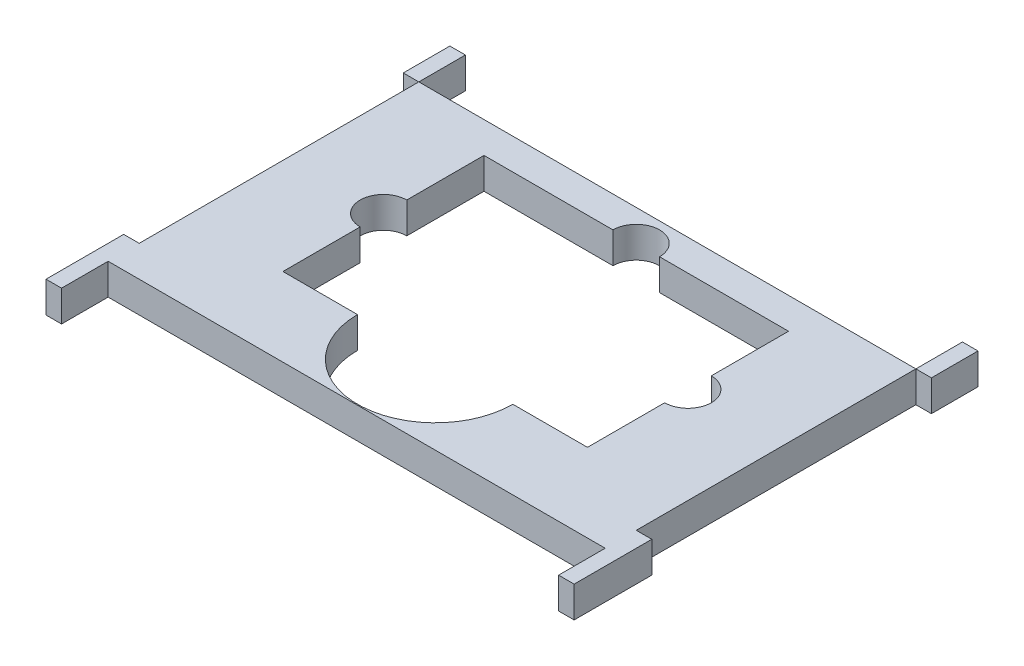
SolidWorks part; units mm, degrees
ref_plane "Front Plane" through (0, 0, 0) normal (0, 0, 1) x (1, 0, 0)
ref_plane "Top Plane" through (0, 0, 0) normal (0, 1, 0) x (1, 0, 0)
ref_plane "Right Plane" through (0, 0, 0) normal (1, 0, 0) x (0, 0, -1)
sketch "Sketch7" plane through (0, 0, 0) normal (0, 1, 0) x (1, 0, 0)
  line L1 (101.6, 63.5) -> (-101.6, 63.5)
  line L2 (101.6, 63.5) -> (101.6, -63.5)
  line L3 (101.6, -63.5) -> (-101.6, -63.5)
  line L4 (-101.6, 63.5) -> (-101.6, -63.5)
  line L5 (0, -63.5) -> (0, 63.5) construction
  line L6 (101.6, 0) -> (-101.6, 0) construction
  line L7 (-62.25, 50.8) -> (62.25, 50.8)
  line L8 (-62.25, 50.8) -> (-62.25, -31.4)
  line L9 (-62.25, -31.4) -> (62.25, -31.4)
  line L10 (62.25, 50.8) -> (62.25, -31.4)
  line L78 (-63.754, 177.8) -> (-101.6, 177.8) construction
  line L79 (63.754, 177.8) -> (101.6, 177.8) construction
  point P0 (0, 0)
  point P4 (0, 50.8)
  dimension "D1" = 124.5
  dimension "D2" = 82.2
  dimension "D3" = 127
  dimension "D9" = 203.2
  dimension "D4" = 12.7
extrude "Boss-Extrude4" add sketch "Sketch7" along normal blind 12.7
sketch "Sketch8" plane through (0, 0, 0) normal (0, 1, 0) x (1, 0, 0)
  line L0 (-101.6, 63.5) -> (-101.6, 69.85)
  line L1 (-101.6, 69.85) -> (-88.9, 69.85)
  line L2 (-88.9, 69.85) -> (-88.9, 63.5)
  line L3 (101.6, 63.5) -> (-101.6, 63.5) construction
  line L4 (-101.6, 63.5) -> (-88.9, 63.5)
  line L5 (-63.5, 63.5) -> (-63.5, 69.85)
  line L6 (-63.5, 69.85) -> (-50.8, 69.85)
  line L7 (-50.8, 69.85) -> (-50.8, 63.5)
  line L8 (-63.5, 63.5) -> (-50.8, 63.5)
  line L9 (-25.4, 63.5) -> (-25.4, 69.85)
  line L10 (-25.4, 69.85) -> (-12.7, 69.85)
  line L11 (-12.7, 69.85) -> (-12.7, 63.5)
  line L12 (-25.4, 63.5) -> (-12.7, 63.5)
  line L13 (12.7, 63.5) -> (12.7, 69.85)
  line L14 (12.7, 69.85) -> (25.4, 69.85)
  line L15 (25.4, 69.85) -> (25.4, 63.5)
  line L16 (12.7, 63.5) -> (25.4, 63.5)
  line L29 (50.8, 63.5) -> (50.8, 69.85)
  line L58 (-101.6, 63.5) -> (-107.95, 63.5)
  line L59 (-101.6, 63.5) -> (-101.6, -63.5) construction
  line L60 (-107.95, 63.5) -> (-107.95, 50.8)
  line L61 (-107.95, 50.8) -> (-101.6, 50.8)
  line L62 (-101.6, 63.5) -> (-101.6, 50.8)
  line L63 (-107.95, 12.7) -> (-101.6, 12.7)
  line L64 (-101.6, 25.4) -> (-101.6, 12.7)
  line L65 (-101.6, 25.4) -> (-107.95, 25.4)
  line L66 (-107.95, 25.4) -> (-107.95, 12.7)
  line L67 (-107.95, -25.4) -> (-101.6, -25.4)
  line L68 (-101.6, -12.7) -> (-101.6, -25.4)
  line L69 (-101.6, -12.7) -> (-107.95, -12.7)
  line L70 (-107.95, -12.7) -> (-107.95, -25.4)
  line L71 (-107.95, -63.5) -> (-101.6, -63.5)
  line L72 (-101.6, -50.8) -> (-101.6, -63.5)
  line L73 (-101.6, -50.8) -> (-107.95, -50.8)
  line L74 (-107.95, -50.8) -> (-107.95, -63.5)
  line L95 (50.8, 69.85) -> (63.5, 69.85)
  line L132 (-107.95, -177.8) -> (-101.6, -177.8) [skipped]
  line L133 (-101.6, -165.1) -> (-101.6, -177.8) [skipped]
  line L134 (-101.6, -165.1) -> (-107.95, -165.1) [skipped]
  line L135 (-107.95, -165.1) -> (-107.95, -177.8) [skipped]
  line L136 (-107.95, -215.9) -> (-101.6, -215.9) [skipped]
  line L137 (-101.6, -203.2) -> (-101.6, -215.9) [skipped]
  line L138 (-101.6, -203.2) -> (-107.95, -203.2) [skipped]
  line L139 (-107.95, -203.2) -> (-107.95, -215.9) [skipped]
  line L140 (-101.6, -241.3) -> (-101.6, -254) [skipped]
  line L141 (-101.6, -241.3) -> (-107.95, -241.3) [skipped]
  line L142 (-107.95, -241.3) -> (-107.95, -254) [skipped]
  line L143 (-107.95, -254) -> (-101.6, -254) [skipped]
  line L144 (63.5, 69.85) -> (63.5, 63.5) [skipped]
  line L145 (88.9, 63.5) -> (88.9, 69.85) [skipped]
  line L146 (88.9, 69.85) -> (101.6, 69.85) [skipped]
  line L147 (101.6, 69.85) -> (101.6, 63.5) [skipped]
  line L148 (88.9, 63.5) -> (101.6, 63.5) [skipped]
  line L149 (50.8, 69.85) -> (63.5, 69.85) [skipped]
  line L150 (50.8, 63.5) -> (63.5, 63.5) [skipped]
  line L151 (50.8, 63.5) -> (50.8, 69.85) [skipped]
  line L152 (127, 63.5) -> (127, 69.85) [skipped]
  line L153 (127, 69.85) -> (139.7, 69.85) [skipped]
  line L154 (127, 63.5) -> (139.7, 63.5) [skipped]
  line L155 (139.7, 69.85) -> (139.7, 63.5) [skipped]
  line L164 (-107.95, -101.6) -> (-101.6, -101.6) [skipped]
  line L165 (-101.6, -88.9) -> (-101.6, -101.6) [skipped]
  line L166 (-101.6, -88.9) -> (-107.95, -88.9) [skipped]
  line L167 (-107.95, -88.9) -> (-107.95, -101.6) [skipped]
  line L168 (-107.95, -139.7) -> (-101.6, -139.7) [skipped]
  line L169 (-101.6, -127) -> (-101.6, -139.7) [skipped]
  line L170 (-101.6, -127) -> (-107.95, -127) [skipped]
  line L171 (-107.95, -127) -> (-107.95, -139.7) [skipped]
  line L196 (63.5, 69.85) -> (63.5, 63.5)
  line L197 (50.8, 63.5) -> (63.5, 63.5)
  line L198 (0, 0) -> (0, -63.5) construction
  line L199 (-101.6, -63.5) -> (101.6, -63.5) construction
  line L200 (0, 0) -> (101.6, 0) construction
  line L201 (101.6, -63.5) -> (101.6, 63.5) construction
  line L202 (107.95, -50.8) -> (107.95, -63.5)
  line L203 (101.6, -50.8) -> (107.95, -50.8)
  line L204 (101.6, -50.8) -> (101.6, -63.5)
  line L205 (107.95, -63.5) -> (101.6, -63.5)
  line L206 (107.95, -12.7) -> (107.95, -25.4)
  line L207 (101.6, -12.7) -> (107.95, -12.7)
  line L208 (101.6, -12.7) -> (101.6, -25.4)
  line L209 (107.95, -25.4) -> (101.6, -25.4)
  line L210 (107.95, 25.4) -> (107.95, 12.7)
  line L211 (101.6, 25.4) -> (107.95, 25.4)
  line L212 (101.6, 25.4) -> (101.6, 12.7)
  line L213 (107.95, 12.7) -> (101.6, 12.7)
  line L214 (101.6, 63.5) -> (101.6, 50.8)
  line L215 (107.95, 50.8) -> (101.6, 50.8)
  line L216 (107.95, 63.5) -> (107.95, 50.8)
  line L217 (101.6, 63.5) -> (107.95, 63.5)
  line L218 (50.8, -63.5) -> (63.5, -63.5)
  line L219 (63.5, -69.85) -> (63.5, -63.5)
  line L220 (50.8, -69.85) -> (63.5, -69.85)
  line L221 (50.8, -63.5) -> (50.8, -69.85)
  line L222 (12.7, -63.5) -> (25.4, -63.5)
  line L223 (25.4, -69.85) -> (25.4, -63.5)
  line L224 (12.7, -69.85) -> (25.4, -69.85)
  line L225 (12.7, -63.5) -> (12.7, -69.85)
  line L226 (-25.4, -63.5) -> (-12.7, -63.5)
  line L227 (-12.7, -69.85) -> (-12.7, -63.5)
  line L228 (-25.4, -69.85) -> (-12.7, -69.85)
  line L229 (-25.4, -63.5) -> (-25.4, -69.85)
  line L230 (-63.5, -63.5) -> (-50.8, -63.5)
  line L231 (-50.8, -69.85) -> (-50.8, -63.5)
  line L232 (-63.5, -69.85) -> (-50.8, -69.85)
  line L233 (-63.5, -63.5) -> (-63.5, -69.85)
  line L234 (-101.6, -63.5) -> (-88.9, -63.5)
  line L235 (-88.9, -69.85) -> (-88.9, -63.5)
  line L236 (-101.6, -69.85) -> (-88.9, -69.85)
  line L237 (-101.6, -63.5) -> (-101.6, -69.85)
  line L238 (88.9, 63.5) -> (88.9, 69.85)
  line L239 (88.9, 69.85) -> (101.6, 69.85)
  line L240 (101.6, 69.85) -> (101.6, 63.5)
  line L241 (88.9, 63.5) -> (101.6, 63.5)
  line L242 (88.9, -63.5) -> (101.6, -63.5)
  line L243 (101.6, -69.85) -> (101.6, -63.5)
  line L244 (88.9, -69.85) -> (101.6, -69.85)
  line L245 (88.9, -63.5) -> (88.9, -69.85)
  dimension "D1" = 12.7
  dimension "D2" = 6.35
  dimension "D3" = 0
  dimension "D4" = 7
  dimension "D5" = 25.4
  dimension "D6" = 3
  dimension "D8" = 0
  dimension "D13" = 25.4
  dimension "D9" = 9
extrude "Boss-Extrude5" add sketch "Sketch8" along normal blind 12.7 rebuild error yes
sketch "Sketch9" plane through (0, 0, 0) normal (0, 1, 0) x (1, 0, 0)
  line L0 (-107.95, 63.5) -> (-107.95, 82.55)
  line L1 (-107.95, 82.55) -> (-101.6, 82.55)
  line L2 (-101.6, 82.55) -> (-101.6, 63.5)
  line L3 (-101.6, 63.5) -> (-107.95, 63.5)
  line L12 (-107.95, -50.8) -> (-107.95, -82.55)
  line L13 (-107.95, -82.55) -> (-101.6, -82.55)
  line L14 (-101.6, -63.5) -> (-101.6, -82.55) construction
  line L15 (-101.6, -82.55) -> (-101.6, -50.8)
  line L16 (-101.6, -50.8) -> (-107.95, -50.8)
  line L17 (-107.95, -50.8) -> (-107.95, -63.5) construction
  line L18 (-101.6, -82.55) -> (-88.9, -82.55) construction
  line L19 (-101.6, -50.8) -> (-107.95, -50.8) construction
  line L30 (0, 0) -> (0, 50.8) construction
  line L31 (62.25, 50.8) -> (-62.25, 50.8) construction
  line L32 (101.6, -50.8) -> (107.95, -50.8)
  line L33 (101.6, -82.55) -> (101.6, -50.8)
  line L34 (107.95, -82.55) -> (101.6, -82.55)
  line L35 (107.95, -50.8) -> (107.95, -82.55)
  line L36 (101.6, 63.5) -> (107.95, 63.5)
  line L37 (101.6, 82.55) -> (101.6, 63.5)
  line L38 (107.95, 82.55) -> (101.6, 82.55)
  line L39 (107.95, 63.5) -> (107.95, 82.55)
extrude "Boss-Extrude6" add sketch "Sketch9" along normal blind 12.7
sketch "Sketch10" plane through (0, 12.7, 0) normal (0, 1, 0) x (1, 0, 0)
  line L0 (62.25, 50.8) -> (-62.25, 50.8) construction
  line L1 (-62.25, 50.8) -> (-62.25, -31.4) construction
  line L2 (-62.25, -31.4) -> (62.25, -31.4) construction
  line L3 (62.25, -31.4) -> (62.25, 50.8) construction
  circle A0 centre (0, 50.8) radius 9.525
  circle A1 centre (-62.25, 9.7) radius 9.525
  circle A2 centre (0, -31.4) radius 31.75
  circle A3 centre (62.25, 9.7) radius 9.525
  dimension "D1" = 19.05
  dimension "D2" = 63.5
extrude "Cut-Extrude1" cut sketch "Sketch10" against normal through all
